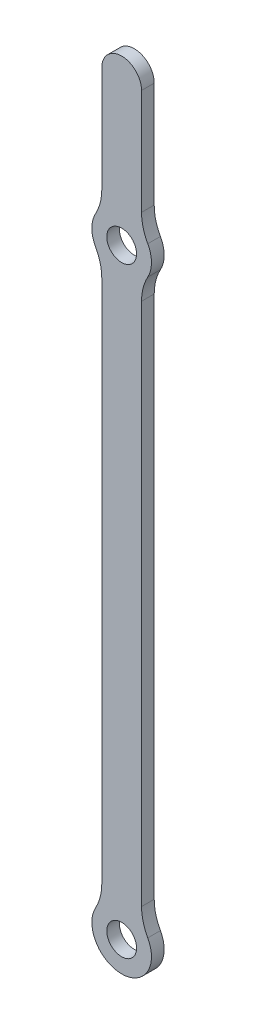
SolidWorks part; units mm, degrees
ref_plane "Front Plane" through (0, 0, 0) normal (0, 0, 1) x (1, 0, 0)
ref_plane "Top Plane" through (0, 0, 0) normal (0, 1, 0) x (1, 0, 0)
ref_plane "Right Plane" through (0, 0, 0) normal (1, 0, 0) x (0, 0, -1)
sketch "Model" plane through (0, 0, 0) normal (0, 0, 1) x (1, 0, 0)
  line L0 (-4, 8.512) -> (-4, 7.746)
  line L1 (4, 8.7857) -> (4, 7.746)
  line L2 (-4, 128.746) -> (-4, 150)
  line L3 (4, 128.746) -> (4, 150)
  line L11 (-4, 113.254) -> (-4, 8.512)
  line L12 (4, 113.254) -> (4, 8.7857)
  circle A0 centre (0, 0) radius 3
  arc A1 (-5.25, 2.9047) -> (5.25, 2.9047) centre (0, 0) ccw
  arc A2 (-4, 7.746) -> (-5.25, 2.9047) centre (-14, 7.746) cw
  arc A3 (4, 7.746) -> (5.25, 2.9047) centre (14, 7.746) ccw
  arc A4 (4, 150) -> (-4, 150) centre (0, 150) ccw
  arc A5 (-5.25, 123.9047) -> (-5.25, 118.0953) centre (0, 121) ccw
  circle A6 centre (0, 121) radius 3
  arc A7 (5.25, 118.0953) -> (5.25, 123.9047) centre (0, 121) ccw
  arc A8 (-5.25, 123.9047) -> (-4, 128.746) centre (-14, 128.746) ccw
  arc A9 (-4, 113.254) -> (-5.25, 118.0953) centre (-14, 113.254) ccw
  arc A10 (4, 113.254) -> (5.25, 118.0953) centre (14, 113.254) cw
  arc A11 (5.25, 123.9047) -> (4, 128.746) centre (14, 128.746) cw
  point P23 (4, 116.5279)
  dimension "D1" = 6
  dimension "D2" = 12
  dimension "D15" = 6
  dimension "D5" = 10
  dimension "D8" = 12
  dimension "D9" = 10
  dimension "D3" = 4
  dimension "D4" = 4
  dimension "D6" = 0
  dimension "D7" = 150
  dimension "D16" = 121
extrude "Boss-Extrude1" add sketch "Model" along normal blind 2.55
